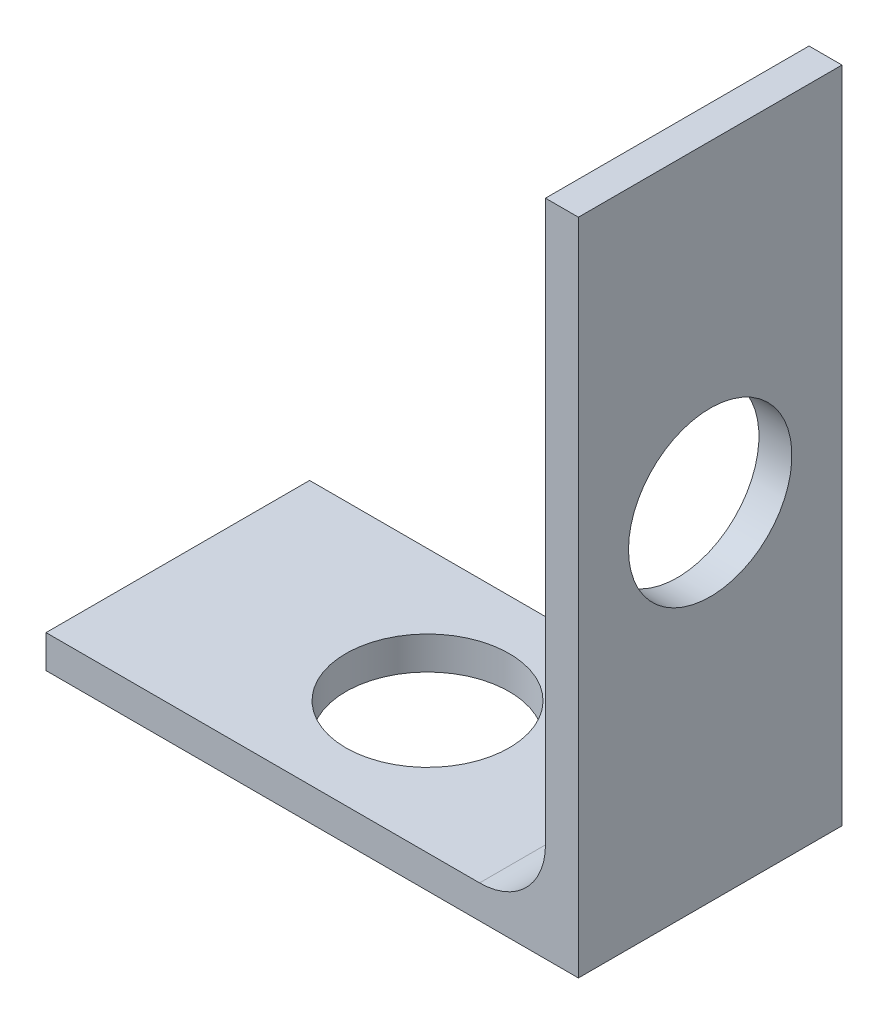
SolidWorks part; units mm, degrees
ref_plane "Front Plane" through (0, 0, 0) normal (0, 0, 1) x (1, 0, 0)
ref_plane "Top Plane" through (0, 0, 0) normal (0, 1, 0) x (1, 0, 0)
ref_plane "Right Plane" through (0, 0, 0) normal (1, 0, 0) x (0, 0, -1)
sketch "Sketch1" plane through (0, 0, 0) normal (0, 0, 1) x (1, 0, 0)
  line L0 (0, 0) -> (25.654, 0)
  line L1 (25.654, 0) -> (25.654, 31.75)
  line L2 (0, 0) -> (0, 1.5875)
  line L3 (0, 1.5875) -> (24.0665, 1.5875)
  line L4 (24.0665, 1.5875) -> (24.0665, 31.75)
  line L5 (24.0665, 31.75) -> (25.654, 31.75)
  dimension "D1" = 31.75
  dimension "D2" = 25.654
  dimension "D3" = 1.5875
  dimension "D4" = 1.5875
extrude "Boss-Extrude1" add sketch "Sketch1" along normal blind 12.7
sketch "Sketch2" plane through (24.0665, 0, 0) normal (-1, 0, 0) x (0, 0, 1)
  line L0 (6.35, 31.75) -> (6.35, 1.5875) construction
  line L1 (12.7, 31.75) -> (0, 31.75) construction
  line L2 (12.7, 1.5875) -> (0, 1.5875) construction
  line L3 (0, 16.6687) -> (12.7, 16.6687) construction
  line L4 (0, 31.75) -> (0, 1.5875) construction
  line L5 (12.7, 31.75) -> (12.7, 1.5875) construction
  circle A0 centre (6.35, 16.6687) radius 3.937
  dimension "D1" = 7.874
extrude "Cut-Extrude1" cut sketch "Sketch2" against normal blind 6.35
sketch "Sketch4" plane through (0, 1.5875, 0) normal (0, 1, 0) x (1, 0, 0)
  line L0 (12.0333, 0) -> (12.0333, -12.7) construction
  line L1 (24.0665, 0) -> (0, 0) construction
  line L2 (24.0665, -12.7) -> (0, -12.7) construction
  line L3 (0, -6.35) -> (24.0665, -6.35) construction
  line L4 (0, -12.7) -> (0, 0) construction
  line L5 (24.0665, -12.7) -> (24.0665, 0) construction
  circle A0 centre (12.0333, -6.35) radius 3.937
  dimension "D1" = 7.874
extrude "Cut-Extrude2" cut sketch "Sketch4" against normal blind 6.35
fillet "Fillet2" radius 3.175 1 edges at (24.0665, 1.5875, 6.35) type face fillet first side face at (24.0665, 16.6687, 10.287) second side face at (12.0333, 1.5875, 10.287)
